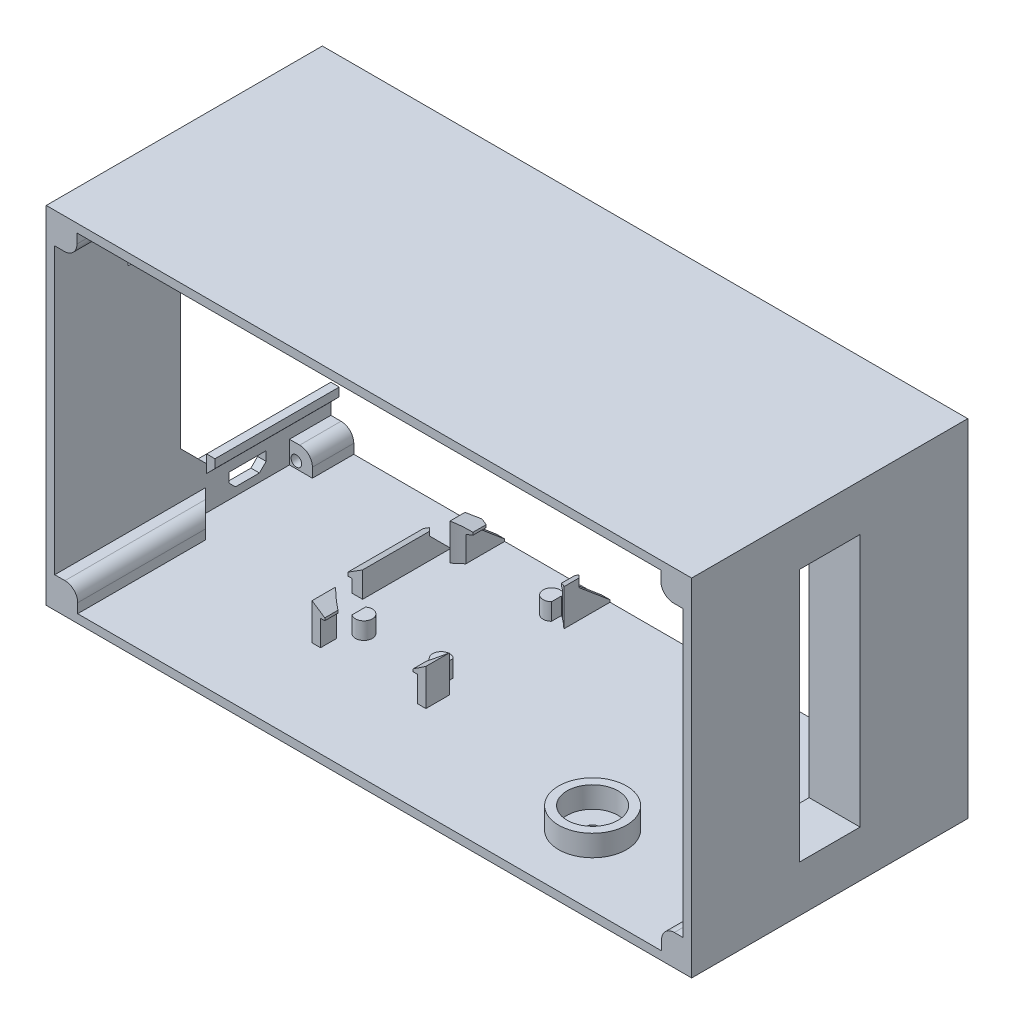
SolidWorks part; units mm, degrees
ref_plane "Plan de face" through (0, 0, 0) normal (0, 0, 1) x (1, 0, 0)
ref_plane "Plan de dessus" through (0, 0, 0) normal (0, 1, 0) x (1, 0, 0)
ref_plane "Plan de droite" through (0, 0, 0) normal (1, 0, 0) x (0, 0, -1)
sketch "Esquisse1" plane through (0, 0, -2.2) normal (0, 0, -1) x (-1, 0, 0)
  line L1 (-32.1075, 39.9055) -> (119.8323, 39.9055)
  line L2 (-32.1075, 39.9055) -> (-32.1075, -41.6387)
  line L3 (-32.1075, -41.6387) -> (119.8323, -41.6387)
  line L4 (119.8323, 39.9055) -> (119.8323, -41.6387)
  line L5 (117.8323, 32.6629) -> (117.8323, -34.3961)
  line L6 (-25.0259, -39.6387) -> (112.4285, -39.6387)
  line L8 (-24.8649, 35.6629) -> (-24.8649, 37.9055)
  line L10 (-27.8649, 32.6629) -> (-30.1075, 32.6629)
  line L12 (-24.8649, 37.9055) -> (112.5896, 37.9055)
  line L13 (-30.1075, 32.6629) -> (-30.1075, -34.3961)
  line L14 (-30.1075, 37.9055) -> (117.8323, 37.9055) construction
  line L15 (112.5896, 37.9055) -> (112.5896, 35.6629)
  line L16 (-30.1075, 37.9055) -> (-30.1075, -39.6387) construction
  line L18 (115.5896, 32.6629) -> (117.8323, 32.6629)
  line L20 (115.4285, -34.3961) -> (117.8323, -34.3961)
  line L21 (117.8323, 37.9055) -> (117.8323, -39.6387) construction
  line L23 (112.4285, -37.3961) -> (112.4285, -39.6387)
  line L24 (-28.0259, -34.3961) -> (-30.1075, -34.3961)
  line L25 (-30.1075, -39.6387) -> (117.8323, -39.6387) construction
  line L27 (-25.0259, -37.3961) -> (-25.0259, -39.6387)
  arc A1 (-27.8649, 32.6629) -> (-24.8649, 35.6629) centre (-27.8649, 35.6629) ccw
  arc A2 (-25.0259, -37.3961) -> (-28.0259, -34.3961) centre (-28.0259, -37.3961) ccw
  arc A3 (115.4285, -34.3961) -> (112.4285, -37.3961) centre (115.4285, -37.3961) ccw
  arc A4 (112.5896, 35.6629) -> (115.5896, 32.6629) centre (115.5896, 35.6629) ccw
  dimension "D1" = 2
extrude "Boss.-Extru.1" add sketch "Esquisse1" along normal blind 65
sketch "Esquisse2" plane through (0, 0, -67.2) normal (0, 0, -1) x (-1, 0, 0)
  line L1 (119.8323, 39.9055) -> (-32.1075, 39.9055)
  line L2 (119.8323, 39.9055) -> (119.8323, -41.6387)
  line L3 (119.8323, -41.6387) -> (-32.1075, -41.6387)
  line L4 (-32.1075, 39.9055) -> (-32.1075, -41.6387)
sketch "Esquisse5" plane through (0, 37.9055, 0) normal (0, -1, 0) x (1, 0, 0)
  circle A0 centre (-16.7337, -61.521) radius 2.8063
  circle A1 centre (-99.3599, -61.521) radius 2.553
  circle A2 centre (-99.3599, -13.1848) radius 2.661
extrude "Boss.-Extru.3" add sketch "Esquisse5" along normal up to surface (5 mm away)
sketch "Esquisse6" plane through (-119.8323, 0, 0) normal (-1, 0, 0) x (0, 0, 1)
  line L0 (-19.9158, 20.4595) -> (-31.8538, 20.4595) construction
  line L1 (-19.4158, 19.9595) -> (-32.3538, 19.9595)
  line L2 (-19.4158, 19.9595) -> (-19.4158, 31.7545)
  line L3 (-19.4158, 31.7545) -> (-32.3538, 31.7545)
  line L4 (-32.3538, 19.9595) -> (-32.3538, 31.7545)
  line L5 (-19.9158, 20.4595) -> (-19.9158, 31.2545) construction
  line L6 (-31.8538, 20.4595) -> (-31.8538, 31.2545) construction
  line L7 (-45.2164, -37.3387) -> (-49.9164, -37.3387) construction
  line L8 (-51.9664, -33.9887) -> (-43.1664, -33.9887)
  line L9 (-51.9664, -33.9887) -> (-51.9664, -36.1637)
  line L10 (-50.3914, -37.7387) -> (-44.7414, -37.7387)
  line L11 (-43.1664, -33.9887) -> (-43.1664, -36.1637)
  line L12 (-51.9664, -36.1637) -> (-50.3914, -37.7387)
  line L13 (-51.7764, -36.1637) -> (-50.9764, -36.1637) construction
  line L14 (-47.5664, -33.9887) -> (-47.5664, -34.2071) construction
  line L15 (-43.1664, -36.1637) -> (-44.7414, -37.7387)
  line L16 (-51.5664, -35.7087) -> (-51.5664, -35.3887) construction
  line L17 (-43.5664, -35.7087) -> (-43.5664, -35.3887) construction
  line L20 (-44.6311, -36.9069) -> (-43.9982, -36.2741) construction
  dimension "D1" = 0.5
  dimension "D2" = 0.5
  dimension "D3" = 0.5
  dimension "D4" = 0.5
  dimension "D5" = 0.4
  dimension "D6" = 0.4
  dimension "D7" = 0.4
  dimension "D8" = 0.4
extrude "Enlèv. mat.-Extru.1" cut sketch "Esquisse6" against normal blind 2
sketch "Esquisse7" plane through (0, -39.6387, 0) normal (0, 1, 0) x (1, 0, 0)
  line L2 (-117.8323, 57.4564) -> (-117.8323, 37.6764)
  line L6 (-117.8323, 37.6764) -> (-111.5896, 37.6764)
  line L7 (-111.5896, 57.4564) -> (-111.5896, 37.6764)
  line L8 (-117.8323, 57.4564) -> (-111.5896, 57.4564)
  line L10 (-118.8323, 57.4564) -> (-118.8323, 37.6764) construction
  line L11 (-117.8323, 38.6764) -> (-112.5896, 38.6764) construction
  line L12 (-112.5896, 56.4564) -> (-112.5896, 38.6764) construction
  line L13 (-117.8323, 56.4564) -> (-112.5896, 56.4564) construction
  line L14 (-117.8323, 56.4564) -> (-117.8323, 38.6764) construction
  line L16 (-118.8323, 37.6764) -> (-111.5896, 37.6764) construction
  line L17 (-118.8323, 57.4564) -> (-111.5896, 57.4564) construction
  dimension "D1" = 1
extrude "Enlèv. mat.-Extru.2" cut sketch "Esquisse7" along normal up to surface (5.2426 mm away) up to face at (-117.031, -34.3961, -38.9888)
fillet "Congé1" radius 3 3 edges at (-99.3599, 37.9055, -15.8458) (-99.3599, 37.9055, -64.074) (-16.7337, 37.9055, -64.3273)
sketch "Esquisse8" plane through (0, -39.6387, 0) normal (0, 1, 0) x (1, 0, 0)
  line L0 (-84.8123, 38.6764) -> (-84.8123, 56.4564) construction
  line L1 (-84.3123, 56.4564) -> (-81.8249, 56.4564)
  line L2 (-84.3123, 56.4564) -> (-84.3123, 38.6764)
  line L3 (-84.3123, 38.6764) -> (-81.8249, 38.6764)
  line L4 (-81.8249, 56.4564) -> (-81.8249, 38.6764)
  line L5 (-84.8123, 56.4564) -> (-117.8323, 56.4564) construction
  line L6 (-117.8323, 38.6764) -> (-84.8123, 38.6764) construction
  dimension "D1" = 0.5
extrude "Boss.-Extru.4" add sketch "Esquisse8" along normal blind 3
sketch "Esquisse9" plane through (0, 0, -56.4564) normal (0, 0, -1) x (-1, 0, 0)
  line L0 (81.8249, -36.6387) -> (85.3123, -36.6387)
  line L1 (85.3123, -36.6387) -> (85.3123, -35.8387)
  line L2 (85.3123, -35.8387) -> (81.8249, -33.6387)
  line L3 (81.8249, -33.6387) -> (81.8249, -36.6387)
  dimension "D1" = 3
  dimension "D2" = 0.8
  dimension "D3" = 1
extrude "Boss.-Extru.5" add sketch "Esquisse9" against normal up to surface (17.78 mm away) up to face at (-83.0686, -38.1387, -38.6764)
chamfer "Chanfrein1" distance 3 angle 45 1 edges at (-83.0686, -39.6387, -56.4564)
sketch "Esquisse10" plane through (0, -39.6387, 0) normal (0, 1, 0) x (1, 0, 0)
  line L0 (-117.8323, 37.6764) -> (-112.4285, 32.2727)
  line L3 (-112.4285, 37.6764) -> (-112.4285, 2.2) construction
  line L5 (-112.4285, 32.2727) -> (-112.4285, 37.6764)
  line L6 (-112.4285, 37.6764) -> (-117.8323, 37.6764)
  point P7 (0, 0)
  point P8 (0, 0)
  dimension "D1" = 45
extrude "Enlèv. mat.-Extru.5" cut sketch "Esquisse10" along normal up to surface (5.2426 mm away) up to face at (-116.6304, -34.3961, -19.9382)
sketch "Esquisse11" plane through (32.1075, 0, 0) normal (1, 0, 0) x (0, 0, -1)
  line L0 (27.95, -30.2966) -> (27.95, 28.5634) construction
  line L1 (27.55, -30.6966) -> (41.85, -30.6966)
  line L2 (27.55, -30.6966) -> (27.55, 28.9634)
  line L3 (27.55, 28.9634) -> (41.85, 28.9634)
  line L4 (41.85, -30.6966) -> (41.85, 28.9634)
  line L5 (41.45, -30.2966) -> (27.95, -30.2966) construction
  line L6 (41.45, 28.5634) -> (41.45, -30.2966) construction
  line L7 (27.95, 28.5634) -> (41.45, 28.5634) construction
  dimension "D1" = 0.4
  dimension "D2" = 0.4
  dimension "D3" = 0.4
  dimension "D4" = 0.4
  dimension "D5" = 14.3
  dimension "D6" = 59.66
extrude "Enlèv. mat.-Extru.6" cut sketch "Esquisse11" against normal blind 10
sketch "Esquisse12" plane through (30.1075, 0, 0) normal (-1, 0, 0) x (0, 0, 1)
  line L0 (-43.85, -32.6966) -> (-43.85, 30.9634)
  line L1 (-41.85, -30.6966) -> (-27.55, -30.6966)
  line L2 (-41.85, -30.6966) -> (-41.85, 28.9634)
  line L3 (-41.85, 28.9634) -> (-27.55, 28.9634)
  line L4 (-27.55, -30.6966) -> (-27.55, 28.9634)
  line L5 (-43.85, 30.9634) -> (-25.55, 30.9634)
  line L6 (-25.55, -32.6966) -> (-25.55, 30.9634)
  line L7 (-43.85, -32.6966) -> (-25.55, -32.6966)
  dimension "D1" = 2
extrude "Boss.-Extru.6" add sketch "Esquisse12" along normal blind 10
sketch "Esquisse13" plane through (0, 30.9634, 0) normal (0, 1, 0) x (1, 0, 0)
  line L0 (30.1075, 43.85) -> (20.1075, 41.85)
  line L1 (20.1075, 41.85) -> (20.1075, 43.85)
  line L2 (20.1075, 43.85) -> (30.1075, 43.85)
extrude "Enlèv. mat.-Extru.7" cut sketch "Esquisse13" against normal up to next
chamfer "Chanfrein3" distance 5 angle 45 1 edges at (30.1075, -0.8666, -43.85)
sketch "Esquisse16" plane through (0, -39.6387, 0) normal (0, 1, 0) x (1, 0, 0)
  circle A1 centre (-56.5068, 31.8489) radius 2
  circle A2 centre (-74.7038, 31.8489) radius 2
  circle A3 centre (-56.5068, 57.8489) radius 2
  dimension "D1" = 4
extrude "Boss.-Extru.8" add sketch "Esquisse16" along normal up to surface (4 mm away)
sketch "Esquisse19" plane through (0, -39.6387, 0) normal (0, 1, 0) x (1, 0, 0)
  line L0 (-54.5068, 42.8489) -> (-54.5068, 23.8489) construction
  line L1 (-54.1068, 23.8489) -> (-52.1068, 23.8489)
  line L2 (-54.1068, 23.8489) -> (-54.1068, 61.8489)
  line L3 (-54.1068, 61.8489) -> (-52.1068, 61.8489)
  line L4 (-52.1068, 23.8489) -> (-52.1068, 61.8489)
  line L5 (-76.9068, 23.8489) -> (-78.9068, 23.8489)
  line L6 (-76.9068, 23.8489) -> (-76.9068, 61.8489)
  line L7 (-76.9068, 61.8489) -> (-78.9068, 61.8489)
  line L8 (-78.9068, 23.8489) -> (-78.9068, 61.8489)
  line L9 (-76.5068, 23.8489) -> (-76.5068, 42.8489) construction
  dimension "D1" = 2
  dimension "D2" = 0.4
  dimension "D3" = 0.4
  dimension "D4" = 2
extrude "Boss.-Extru.10" add sketch "Esquisse19" along normal up to surface (5.6 mm away)
sketch "Esquisse20" plane through (0, 0, -61.8489) normal (0, 0, -1) x (-1, 0, 0)
  line L0 (54.1068, -34.0387) -> (76.9068, -34.0387) construction
  line L1 (52.1068, -34.0387) -> (52.1068, -31.0387)
  line L2 (52.1068, -31.0387) -> (55.1068, -33.0387)
  line L3 (55.1068, -33.0387) -> (55.1068, -33.6387)
  line L4 (55.1068, -33.6387) -> (54.1068, -33.6387)
  line L5 (54.1068, -33.6387) -> (54.1068, -34.0387)
  line L6 (54.1068, -34.0387) -> (52.1068, -34.0387)
  line L7 (65.5068, -34.0387) -> (65.5068, -30.7656) construction
  line L8 (76.9068, -34.0387) -> (78.9068, -34.0387)
  line L9 (76.9068, -33.6387) -> (76.9068, -34.0387)
  line L10 (75.9068, -33.6387) -> (76.9068, -33.6387)
  line L11 (75.9068, -33.0387) -> (75.9068, -33.6387)
  line L12 (78.9068, -31.0387) -> (75.9068, -33.0387)
  line L13 (78.9068, -34.0387) -> (78.9068, -31.0387)
  dimension "D1" = 3
  dimension "D2" = 0.6
  dimension "D3" = 0.4
  dimension "D4" = 1
extrude "Boss.-Extru.11" add sketch "Esquisse20" against normal up to vertex (38 mm away) up to point (-52.1068, -34.0387, -23.8489)
sketch "Esquisse22" plane through (0, -39.6387, 0) normal (0, 1, 0) x (1, 0, 0)
  circle A0 centre (-7.7148, 18.7007) radius 6
  circle A1 centre (-7.7148, 18.7007) radius 8
  dimension "D1" = 2
extrude "Boss.-Extru.12" add sketch "Esquisse22" along normal blind 5
sketch "Esquisse23" plane through (0, -41.6387, 0) normal (0, -1, 0) x (1, 0, 0)
  circle A0 centre (-7.7148, -18.7007) radius 1.5
  dimension "D1" = 3
extrude "Enlèv. mat.-Extru.8" cut sketch "Esquisse23" against normal blind 5
chamfer "Chanfrein4" distance 5 angle 50 2 edges at (-53.1068, -39.6387, -61.8489) (-77.9068, -39.6387, -61.8489)
ref_plane "Plan1" through (-78.9068, -31.0387, -61.8489) normal (0, 0, -1) x (-1, 0, 0)
sketch "Esquisse25" plane through (0, -35.6387, 0) normal (0, 1, 0) x (1, 0, 0)
  line L0 (-52.1068, 29.3789) -> (-52.1068, 56.3188)
  line L3 (-78.9068, 29.3789) -> (-78.9068, 56.3188)
  line L4 (-55.1068, 58.7498) -> (-55.1068, 26.9479)
  line L5 (-75.9068, 26.9479) -> (-75.9068, 58.7498)
  line L6 (-52.1068, 23.8489) -> (-52.1068, 61.8489) construction
  line L7 (-78.9068, 23.8489) -> (-78.9068, 61.8489) construction
  line L8 (-55.1068, 23.8489) -> (-55.1068, 61.8489) construction
  line L9 (-75.9068, 23.8489) -> (-75.9068, 61.8489) construction
  arc A0 (-55.1068, 26.9479) -> (-52.1068, 29.3789) centre (-65.5068, 42.8489) ccw
  arc A1 (-75.9068, 58.7498) -> (-78.9068, 56.3188) centre (-65.5068, 42.8489) ccw
  arc A2 (-52.1068, 56.3188) -> (-55.1068, 58.7498) centre (-65.5068, 42.8489) ccw
  arc A3 (-78.9068, 29.3789) -> (-75.9068, 26.9479) centre (-65.5068, 42.8489) ccw
extrude "Enlèv. mat.-Extru.9" cut sketch "Esquisse25" along normal up to vertex and the other way up to surface
chamfer "Chanfrein5" distance 2 angle 45 3 edges at (-78.9068, -32.8387, -61.8489) (-52.1068, -32.8387, -61.8489) (-81.8249, -35.1387, -56.4564)
sketch "Esquisse26" plane through (-119.8323, 0, 0) normal (-1, 0, 0) x (0, 0, 1)
  line L0 (-67.2, 39.9055) -> (-67.2, -41.6387) construction
  line L1 (-37.9518, 15.075) -> (-31.8, 8.9231)
  line L2 (-67.2, 15.075) -> (-37.9518, 15.075)
  line L3 (-67.2, 15.075) -> (-67.2, -29.6387)
  line L4 (-67.2, -29.6387) -> (-37.9518, -29.6387)
  line L5 (-31.8, 8.9231) -> (-31.8, -23.4869)
  line L6 (-31.8, -23.4869) -> (-37.9518, -29.6387)
  line L8 (-67.2, -41.6387) -> (-2.2, -41.6387) construction
  line L9 (-67.2, -7.2819) -> (-31.8, -7.2819) construction
  point P13 (0, 0)
  point P15 (0, 0)
  dimension "D1" = 135
  dimension "D2" = 135
  dimension "D3" = 12
  dimension "D4" = 44.7137
  dimension "D5" = 32.41
  dimension "D6" = 29.2482
extrude "Enlèv. mat.-Extru.10" cut sketch "Esquisse26" against normal blind 2
sketch "Esquisse27" plane through (0, 0, -67.2) normal (0, 0, -1) x (-1, 0, 0)
  line L0 (121.2223, 18.465) -> (117.8323, 18.465)
  line L2 (117.8323, 15.075) -> (117.8323, 32.6629) construction
  line L3 (117.8323, 15.075) -> (117.8323, 18.465)
  circle A0 centre (121.2223, 15.075) radius 1
  arc A1 (117.8323, 15.075) -> (121.2223, 18.465) centre (121.2223, 15.075) ccw
  point P9 (117.8323, 18.3951)
  line M2 (117.8323, 15.075) -> (119.8323, 15.075)
  line M3 (119.8323, 15.075) -> (119.8323, 39.9055)
  dimension "D1" = 2
extrude "Boss.-Extru.13" add sketch "Esquisse27" against normal up to vertex (29.2482 mm away) contours A1 L0 A0 M2 M3 up to point (-119.8323, 15.0749, -37.9518)
sketch "Esquisse28" plane through (0, 0, -67.2) normal (0, 0, -1) x (-1, 0, 0)
  circle A0 centre (121.2223, 15.075) radius 4.19
  arc A1 (117.8323, 15.075) -> (121.2223, 18.465) centre (121.2223, 15.075) ccw construction
  dimension "D1" = 0.8
extrude "Enlèv. mat.-Extru.11" cut sketch "Esquisse28" against normal blind 10 from offset 10 offset against normal yes
sketch "Esquisse29" plane through (0, 0, -67.2) normal (0, 0, -1) x (-1, 0, 0)
  line L0 (117.8323, -27.6387) -> (115.8603, -27.6387)
  line L1 (115.8603, -27.6387) -> (115.8603, -29.6387)
  line L2 (115.8603, -29.6387) -> (117.8323, -31.6387)
  line L3 (117.8323, -34.3961) -> (117.8323, -29.6387) construction
  line L4 (117.8323, -29.6387) -> (119.8323, -29.6387) construction
  line L5 (117.8323, -27.6387) -> (117.8323, -31.6387)
  point P2 (117.8323, -31.3078)
  dimension "D1" = 2
  dimension "D2" = 2
  dimension "D3" = 2
extrude "Boss.-Extru.14" add sketch "Esquisse29" against normal up to vertex (29.2482 mm away) up to point (-117.8323, -29.6387, -37.9518)
sketch "Esquisse30" plane through (0, 0, -37.9518) normal (0, 0, 1) x (1, 0, 0)
  circle A0 centre (-121.2223, 15.075) radius 1
extrude "Boss.-Extru.15" add sketch "Esquisse30" against normal blind 2
sketch "Esquisse31" plane through (0, 0, -67.2) normal (0, 0, -1) x (-1, 0, 0)
  circle A0 centre (116.211, -38.0174) radius 1.25
  circle A1 centre (-28.4862, -38.0174) radius 1.25
  circle A2 centre (-28.4862, 36.2842) radius 1.25
  circle A3 centre (116.211, 36.2842) radius 1.25
  dimension "D1" = 2.5
extrude "Enlèv. mat.-Extru.12" cut sketch "Esquisse31" against normal blind 15
